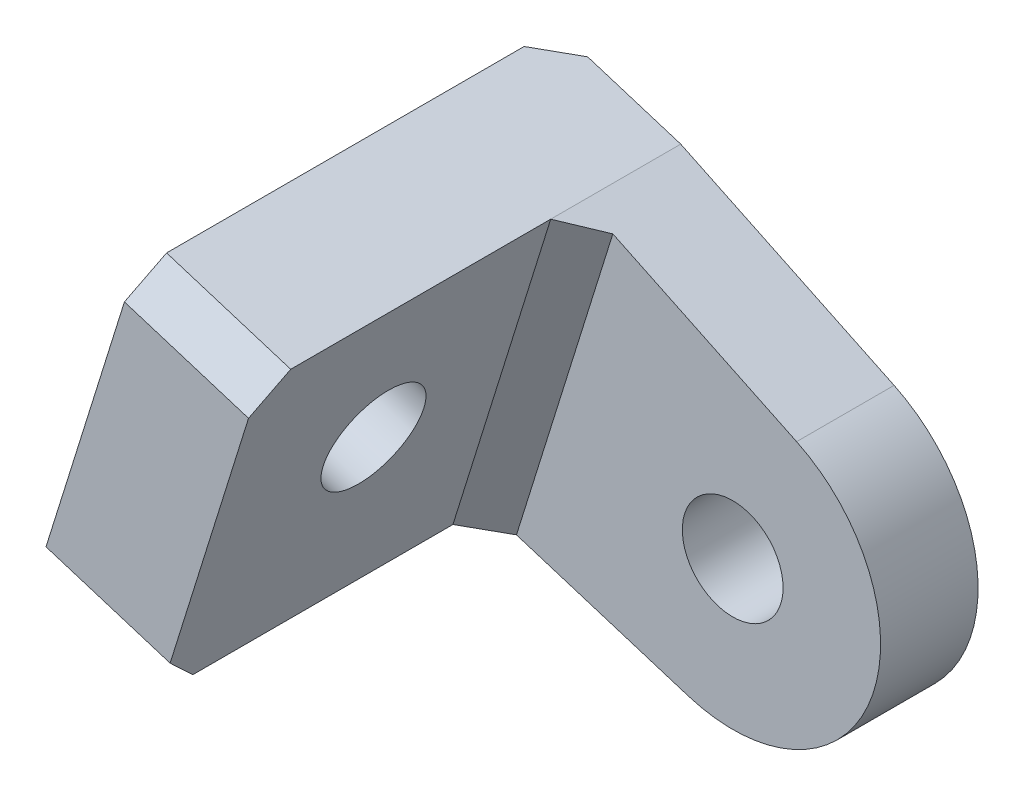
SolidWorks part; units mm, degrees
ref_plane "Front Plane" through (0, 0, 0) normal (0, 0, 1) x (1, 0, 0)
ref_plane "Top Plane" through (0, 0, 0) normal (0, 1, 0) x (1, 0, 0)
ref_plane "Right Plane" through (0, 0, 0) normal (1, 0, 0) x (0, 0, -1)
sketch "Sketch1" plane through (0, 0, 0) normal (0, 0, 1) x (1, 0, 0)
  line L0 (4.5872, 32.0905) -> (13.1786, 29.4093) construction
  line L1 (4.5872, 32.0905) -> (13.1786, 29.4093)
  line L2 (4.5872, 32.0905) -> (1.3298, 21.6525)
  line L3 (7.2749, 23.9188) -> (2.9315, 25.2743) construction
  line L4 (2.9315, 25.2743) -> (0.0677, 26.168) construction
  line L5 (7.2749, 23.9188) -> (8.6304, 28.2622) construction
  line L6 (8.6304, 28.2622) -> (-1.4406, 31.4051)
  line L7 (0.0677, 26.168) -> (-2.7961, 27.0617) construction
  line L8 (-2.7961, 27.0617) -> (-1.4406, 31.4051)
  line L9 (7.2749, 23.9188) -> (5.9194, 19.5754) construction
  line L10 (5.9194, 19.5754) -> (-4.1516, 22.7183)
  line L11 (-2.7961, 27.0617) -> (-4.1516, 22.7183)
  line L12 (-1.4406, 31.4051) -> (-1.1427, 32.3597)
  line L13 (-1.1427, 32.3597) -> (2.6757, 31.1681)
  line L14 (2.6757, 31.1681) -> (2.3777, 30.2135)
  line L15 (2.6757, 31.1681) -> (9.2411, 28.022)
  circle A0 centre (7.2749, 23.9188) radius 1.55
  circle A1 centre (7.2749, 23.9188) radius 4.55
  dimension "D1" = 3.1
  dimension "D2" = 9.1
  dimension "D3" = 3
  dimension "D4" = 3
  dimension "D5" = 1
  dimension "D6" = 4
extrude "Boss-Extrude1" add sketch "Sketch1" along normal blind 3 contours A1 A0 | A1 L6 L8 L11 L10 | L14 L13 L12 L6 | L15 L14 L6 L2 | A1 L15 L2 L6 region at (5.6341, 29.4674, 0) region at (3.2191, 30.4182, 0) region at (0.6043, 26.0005, 0) region at (0.6175, 31.2866, 0) region at (11.0162, 26.2747, 0)
sketch "Sketch2" plane through (0, 0, 3) normal (0, 0, 1) x (1, 0, 0)
  line L0 (-1.1427, 32.3597) -> (-4.1516, 22.7183)
  line L1 (-4.1516, 22.7183) -> (-0.3332, 21.5267)
  line L2 (5.9194, 19.5754) -> (-4.1516, 22.7183) construction
  line L3 (-0.3332, 21.5267) -> (2.6757, 31.1681)
  line L5 (-1.1427, 32.3597) -> (2.6757, 31.1681)
  dimension "D1" = 4
extrude "Boss-Extrude2" add sketch "Sketch2" along normal blind 10
sketch "Sketch3" plane through (-10.2437, 3.1968, 0) normal (-0.9546, 0.2979, 0) x (0, 0, 1)
  ellipse E0 centre (8.0559, 25.8577) end of major axis (6.5059, 25.8577) minor radius 1.55 construction
  ellipse E1 centre (8.0559, 25.8577) end of major axis (6.5059, 25.8577) minor radius 1.55
extrude "Cut-Extrude1" cut sketch "Sketch3" against normal up to next
chamfer "Chamfer1" distance 1 angle 45 2 edges at (-2.2424, 22.1225, 13) (0.7665, 31.7639, 13)
chamfer "Chamfer2" distance 1 angle 45 1 edges
chamfer "Chamfer3" distance 1 angle 45 1 edges at (-2.6471, 27.539, 0)
